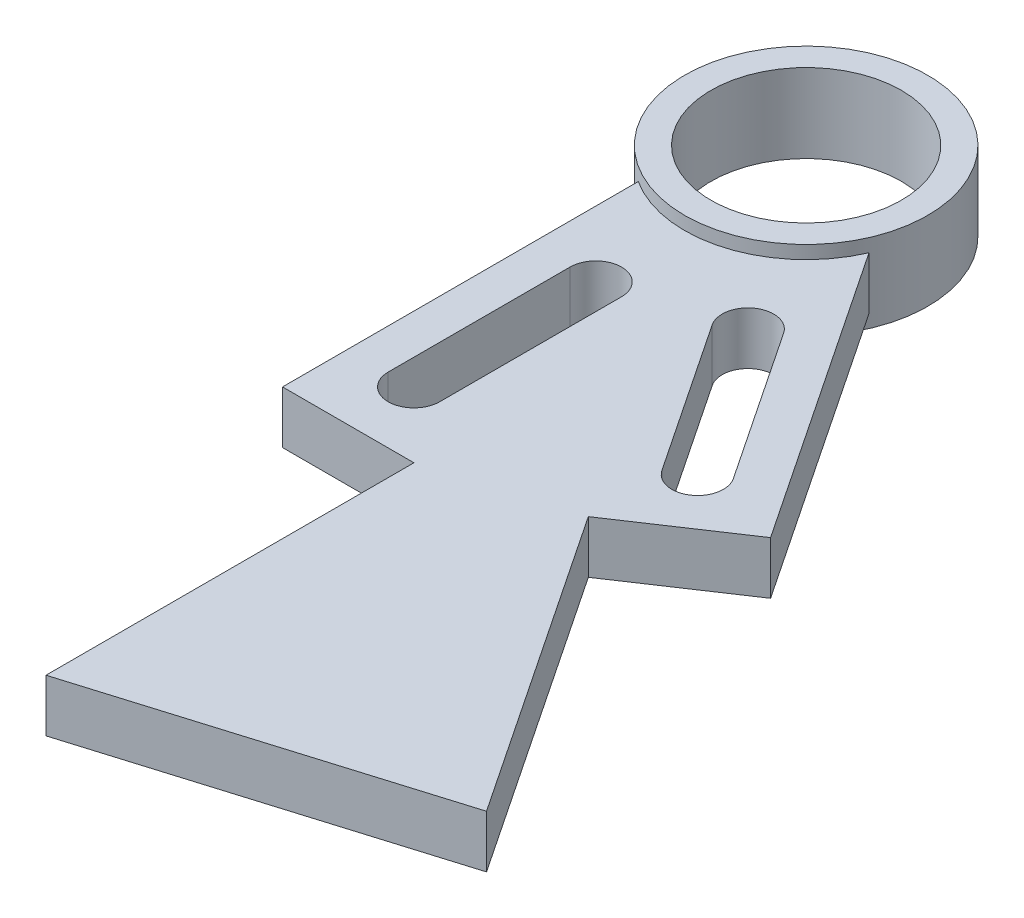
SolidWorks part; units mm, degrees
material "AISI 4130 Steel, normalized at 870C"
ref_plane "Front Plane" through (0, 0, 0) normal (0, 0, 1) x (1, 0, 0)
ref_plane "Top Plane" through (0, 0, 0) normal (0, 1, 0) x (1, 0, 0)
ref_plane "Right Plane" through (0, 0, 0) normal (1, 0, 0) x (0, 0, -1)
sketch "Sketch1" plane through (0, 0, 0) normal (0, 1, 0) x (1, 0, 0)
  line L0 (0, -50.4952) -> (0, -14.6812) construction
  line L1 (28.0293, -42.0015) -> (8.1494, -12.2117) construction
  line L2 (0, -47.3837) -> (0, -25.4127) construction
  line L5 (-3.1115, -47.3837) -> (-3.1115, -25.4127)
  line L8 (-7.9375, -55.3212) -> (7.9375, -55.3212)
  line L9 (24.1058, -50.4217) -> (37.3105, -41.6097)
  line L10 (-7.9375, -55.3212) -> (-7.9375, -12.3505)
  line L11 (37.3105, -41.6097) -> (13.4579, -5.867)
  line L12 (7.9375, -55.3212) -> (7.9375, -99.7712)
  line L13 (24.1058, -50.4217) -> (48.7795, -87.3948)
  line L14 (7.9375, -99.7712) -> (48.7795, -87.3948)
  line L15 (0, -14.6812) -> (0, 0) construction
  line L16 (0, -55.3212) -> (0, -50.4952) construction
  line L17 (30.7082, -46.0157) -> (28.0293, -42.0015)
  line L18 (3.1115, -47.3837) -> (3.1115, -25.4127)
  line L19 (14.1063, -21.1381) -> (26.3021, -39.4134) construction
  line L20 (16.6944, -19.4109) -> (28.8903, -37.6862)
  line L21 (11.5182, -22.8652) -> (23.714, -41.1405)
  line L22 (8.1494, -12.2117) -> (0, 0) construction
  line L23 (0, 0) -> (19.1521, -63.2019) construction
  line L25 (175.0809, -262.3561) -> (14.5398, -21.7877) construction
  line L27 (0, 0) -> (28.3585, -93.583) construction
  circle A0 centre (0, 0) radius 11.5062
  circle A1 centre (0, 0) radius 14.6812
  arc A2 (-3.1115, -47.3837) -> (3.1115, -47.3837) centre (0, -47.3837) ccw
  arc A3 (3.1115, -25.4127) -> (-3.1115, -25.4127) centre (0, -25.4127) ccw
  arc A4 (16.6944, -19.4109) -> (11.5182, -22.8652) centre (14.1063, -21.1381) ccw
  arc A5 (23.714, -41.1405) -> (28.8903, -37.6862) centre (26.3021, -39.4134) ccw
  point P9 (0, -36.3982)
  point P14 (20.2042, -30.2757)
  point P23 (0, -55.3212)
  point P26 (30.7082, -46.0157)
  point P33 (0, -50.4952)
  point P36 (28.0293, -42.0015)
  point P38 (0, -22.3012)
  dimension "D2" = 29.3624
  dimension "D3" = 40.64
  dimension "D4" = 4.826
  dimension "D6" = 44.45
  dimension "D7" = 7.9375
  dimension "D5" = 4.826
  dimension "D8" = 7.62
  dimension "D9" = 66.04
extrude "Bearing extrude" add sketch "Sketch1" along normal mid plane 9.525 contours A1 A0 region at (-6.8368, 0, -12.521)
extrude "Boss-Extrude2" add sketch "Sketch1<5>" along normal mid plane 6.35 contours A1 L10 L8 L12 L14 L13 L9 L11 A4 A2 region at (17.0045, 0, 56.1148)
sketch "Sketch1<5>" plane through (0, 0, 0) normal (0, 1, 0) x (1, 0, 0) same geometry as "Sketch1"
sketch3d "Tab Point"
  line L0 (19.1521, 0, 63.2019) -> (19.1521, 25.4, 63.2019) construction
  line L1 (0, 0, 0) -> (19.1521, 0, 63.2019) construction
  line L2 (0, 0, 0) -> (28.3585, 0, 93.583) construction
  dimension "D1" = 25.4
equation "\"Apex_thickness\"= .25"
equation "\"Bearing_diameter\"= .906"
equation "\"A-arm_angle\"= 32.91"
equation "\"D1@Sketch1\"=\"Bearing_diameter\""
equation "\"D1@Boss-Extrude2\"= \"Apex_thickness\""
equation "\"apex slot\"= 1.4"
equation "\"tube diameter\"= 5 / 8"
